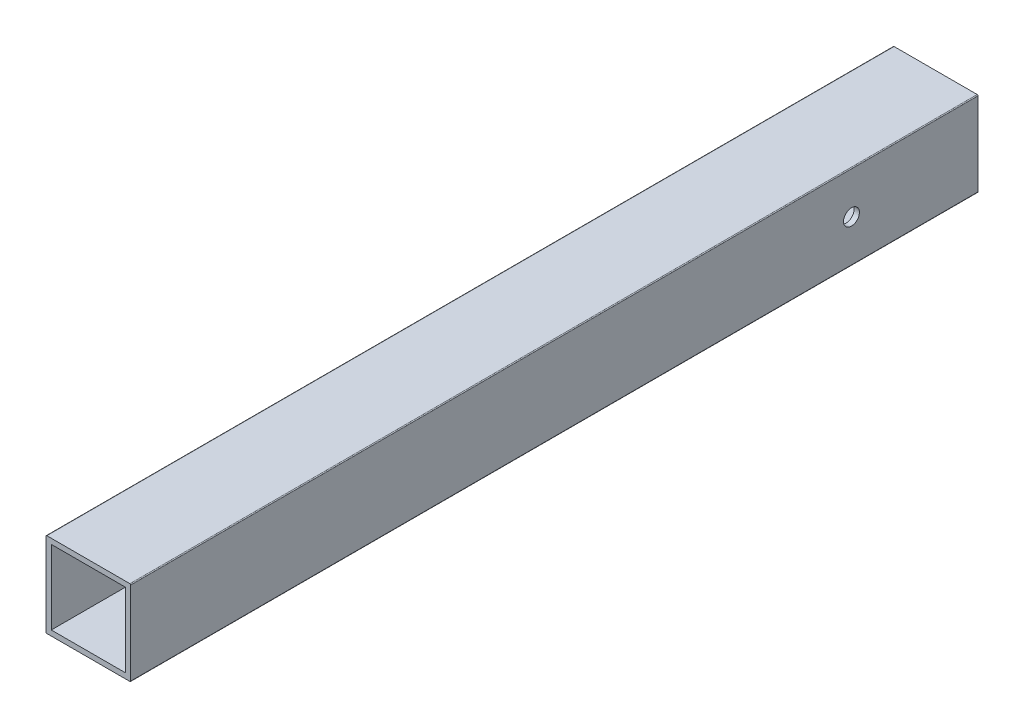
SolidWorks part; units mm, degrees
material "1060 Alloy"
ref_plane "Front Plane" through (0, 0, 0) normal (0, 0, 1) x (1, 0, 0)
ref_plane "Top Plane" through (0, 0, 0) normal (0, 1, 0) x (1, 0, 0)
ref_plane "Right Plane" through (0, 0, 0) normal (1, 0, 0) x (0, 0, -1)
ref_plane "Plane1" through (0, 0, 0) normal (0, 0, -1) x (-1, 0, 0)
sketch "Sketch1" plane through (0, 0, 0) normal (0, 0, -1) x (-1, 0, 0)
  line L4 (1.5875, -1.3335) -> (1.5875, 23.5585)
  line L5 (1.3335, 23.8125) -> (-23.5585, 23.8125)
  line L6 (-23.8125, 23.5585) -> (-23.8125, -1.3335)
  line L7 (-23.5585, -1.5875) -> (1.3335, -1.5875)
  line L9 (0, 22.225) -> (-22.225, 22.225)
  line L10 (0, 22.225) -> (0, 0)
  line L11 (0, 0) -> (-22.225, 0)
  line L12 (-22.225, 22.225) -> (-22.225, 0)
  line L13 (0, 22.225) -> (-22.225, 0) construction
  line L14 (0, 0) -> (-22.225, 22.225) construction
  arc A4 (1.3335, -1.5875) -> (1.5875, -1.3335) centre (1.3335, -1.3335) ccw
  arc A5 (1.5875, 23.5585) -> (1.3335, 23.8125) centre (1.3335, 23.5585) ccw
  arc A6 (-23.5585, 23.8125) -> (-23.8125, 23.5585) centre (-23.5585, 23.5585) ccw
  arc A7 (-23.8125, -1.3335) -> (-23.5585, -1.5875) centre (-23.5585, -1.3335) ccw
  point P24 (-11.1125, 11.1125)
  dimension "D1" = 25.4
  dimension "D2" = 25.4
  dimension "D3" = 1.5875
  dimension "D4" = 1.5875
  dimension "D5" = 1.5875
extrude "Boss-Extrude1" add sketch "Sketch1" against normal blind 254
sketch "Sketch2" plane through (-1.5875, 0, 0) normal (-1, 0, 0) x (0, 0, 1)
  line L0 (0, -1.3335) -> (0, 23.5585) construction
  line L1 (254, -1.3335) -> (0, -1.3335) construction
  line L2 (254, -1.3335) -> (254, 23.5585) construction
  circle A0 centre (12.6975, 11.3665) radius 1.5875
  circle A1 centre (241.3, 11.3665) radius 1.5875
  circle A2 centre (76.2, 11.3665) radius 6.35
  circle A3 centre (177.8, 11.3665) radius 6.35
  point P4 (0, 11.1125)
  dimension "D1" = 3.175
  dimension "D2" = 12.7
  dimension "D3" = 12.7
  dimension "D4" = 3.175
  dimension "D5" = 12.7
  dimension "D6" = 12.7
  dimension "D7" = 12.7
  dimension "D8" = 12.7
  dimension "D9" = 76.2
  dimension "D10" = 12.7
  dimension "D11" = 12.7
  dimension "D12" = 76.2
extrude "Cut-Extrude1" [suppressed] cut sketch "Sketch2" against normal through all
sketch "Sketch4" plane through (23.8125, 0, 0) normal (1, 0, 0) x (0, 0, -1)
  line L7 (-40.3145, 11.1125) -> (-35.552, 11.1125)
  line L8 (0, 23.5585) -> (0, -1.3335) construction
  line L9 (0, 11.1125) -> (-49.6378, 11.1125)
  circle A2 centre (-37.9333, 11.1125) radius 2.3812
  dimension "D1" = 4.7625
extrude "Cut-Extrude2" cut sketch "Sketch4" against normal through all contours A2
